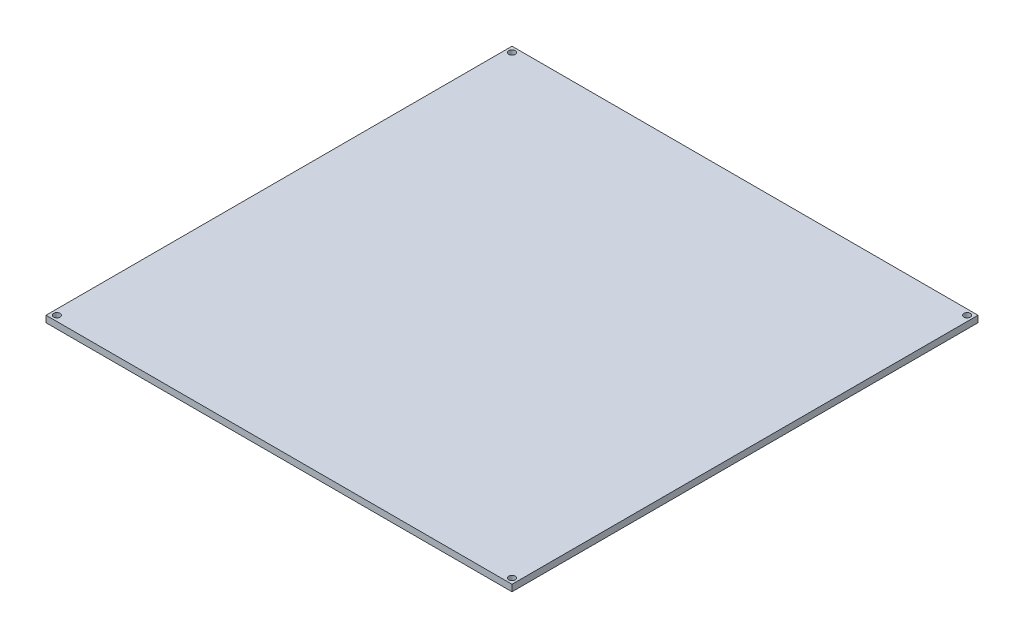
SolidWorks part; units mm, degrees
material "6061-T6 (SS)"
ref_plane "Front Plane" through (0, 0, 0) normal (0, 0, 1) x (1, 0, 0)
ref_plane "Top Plane" through (0, 0, 0) normal (0, 1, 0) x (1, 0, 0)
ref_plane "Right Plane" through (0, 0, 0) normal (1, 0, 0) x (0, 0, -1)
sketch "Sketch1" plane through (0, 0, 0) normal (0, 1, 0) x (1, 0, 0)
  line L0 (107, -107) -> (107, 107)
  line L1 (107, 107) -> (-107, 107)
  line L2 (-107, 107) -> (-107, -107)
  line L3 (-107, -107) -> (107, -107)
  line L4 (0, 107) -> (0, -107) construction
  line L5 (-107, 0) -> (107, 0) construction
  circle A0 centre (104.5, 104.5) radius 1.5
  circle A1 centre (-104.5, -104.5) radius 1.5
  circle A2 centre (104.5, -104.5) radius 1.5
  circle A3 centre (-104.5, 104.5) radius 1.5
  dimension "D2" = 209
  dimension "D3" = 209
  dimension "D4" = 3
  dimension "D1" = 214
extrude "Boss-Extrude1" add sketch "Sketch1" against normal blind 3
